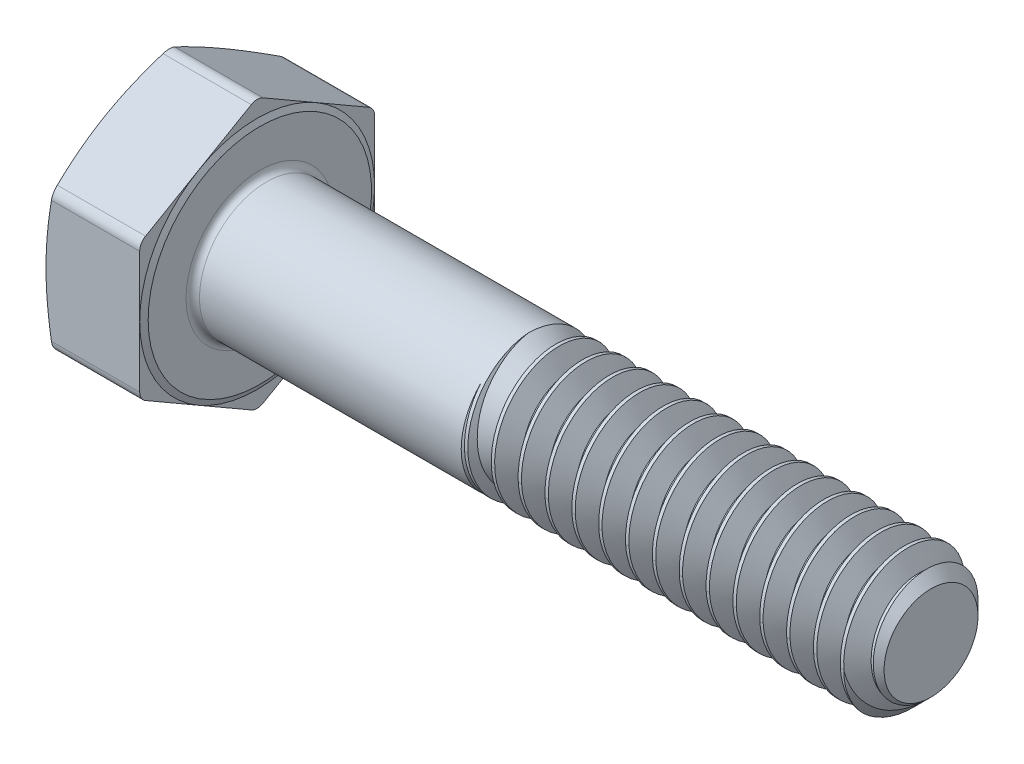
SolidWorks part; units mm, degrees
ref_plane "Front Plane" through (0, 0, 0) normal (0, 0, 1) x (1, 0, 0)
ref_plane "Top Plane" through (0, 0, 0) normal (0, 1, 0) x (1, 0, 0)
ref_plane "Right Plane" through (0, 0, 0) normal (1, 0, 0) x (0, 0, -1)
sketch "Sketch1" plane through (0, 0, 0) normal (0, 0, 1) x (1, 0, 0)
  line L0 (0, 0) -> (31.75, 0) construction
  line L1 (0, 0) -> (-4.7625, 0) construction
  line L2 (0, 5.5562) -> (0, -5.5562) construction
  line L3 (-4.7625, 5.5562) -> (-4.7625, -5.5563) construction
  line L4 (31.75, 3.175) -> (31.75, -3.175) construction
  line L5 (12.7, 3.175) -> (12.7, -3.175) construction
  line L8 (30.48, 3.175) -> (31.75, 3.175) construction
  point P8 (30.48, 0)
  point P11 (27.305, -3.175)
  point P12 (12.7, 0)
  point P15 (4.445, 0)
  point P16 (8.255, 0)
  dimension "Head Height" = 4.7625
  dimension "Head Width" = 11.1125
  dimension "Length" = 31.75
  dimension "Thread Size" = 6.35
  dimension "D1" = 4.445
  dimension "Thread Pitch" = 1.27
  dimension "Min. Thread Length" = 19.05
  dimension "D2" = 4.445
  dimension "D3" = 4.445
sketch "Sketch2" plane through (0, 0, 0) normal (1, 0, 0) x (0, 0, -1)
  circle A0 centre (0, 0) radius 3.175
extrude "Boss-Extrude1" add sketch "Sketch2" along normal up to vertex (31.75 mm away) up to point (31.75, 3.175, 0)
sketch "Sketch3" plane through (0, 0, 0) normal (-1, 0, 0) x (0, 0, 1)
  line L0 (0, 6.4158) -> (0, 0) construction
  line L1 (0, 6.4158) -> (-5.5562, 3.2079)
  line L2 (-5.5562, 3.2079) -> (-5.5562, -3.2079)
  line L3 (-5.5562, -3.2079) -> (0, -6.4158)
  line L4 (0, -6.4158) -> (5.5562, -3.2079)
  line L5 (5.5562, -3.2079) -> (5.5563, 3.2079)
  line L6 (5.5563, 3.2079) -> (0, 6.4158)
  circle A0 centre (0, 0) radius 5.5562 construction
extrude "Boss-Extrude2" add sketch "Sketch3" along normal up to vertex (4.7625 mm away) up to point (-4.7625, 5.5562, 0)
sketch "Sketch5" plane through (-4.7625, 0, 0) normal (-1, 0, 0) x (0, 0, 1)
  circle A0 centre (0, 0) radius 5.5562 construction
  circle A1 centre (0, 0) radius 5.5562 construction
  circle A2 centre (0, 0) radius 5.0006
  dimension "D1" = 0.5556
extrude "Cut-Extrude1" cut sketch "Sketch5" against normal up to vertex (4.7625 mm away) draft 70 flip side to cut up to point (0, 0, 0)
sketch "Sketch11" plane through (-4.7625, 0, 0) normal (-1, 0, 0) x (0, 0, 1)
  line L0 (0, 4.6672) -> (0, 2.9726) construction
  line L1 (0.1945, 4.6672) -> (0.1945, 2.9726)
  line L2 (-0.1945, 4.6672) -> (-0.1945, 2.9726)
  arc A0 (0.1945, 4.6672) -> (-0.1945, 4.6672) centre (0, 4.6672) ccw
  arc A1 (-0.1945, 2.9726) -> (0.1945, 2.9726) centre (0, 2.9726) ccw
  circle A2 centre (0, 0) radius 4.8617 construction
  circle A3 centre (0, 0) radius 2.7781 construction
  point P3 (0, 3.8199)
  dimension "D1" = 9.7234
  dimension "D2" = 5.5562
  dimension "D3" = 0.3889
extrude "Boss-Extrude5" add sketch "Sketch11" along normal blind 0.0635
fillet "Fillet5" radius 0.0635 4 edges at (-4.826, 3.8199, 0.1945) (-4.826, 2.7781, 0) (-4.826, 3.8199, -0.1945) (-4.826, 4.8617, 0)
fillet "Fillet6" radius 0.0635 4 edges at (-4.7625, 2.7781, 0) (-4.7625, 3.8199, -0.1945) (-4.7625, 4.8617, 0) (-4.7625, 3.8199, 0.1945)
pattern_circular "CirPattern1" count 9 over 360 about axis through (0, 0, 0) along (-1, 0, 0) of "Boss-Extrude5", "Fillet5", "Fillet6" reverse direction yes
sketch "Sketch16" plane through (-4.7625, 0, 0) normal (-1, 0, 0) x (0, 0, 1)
  circle A0 centre (0, 0) radius 2.5003
  dimension "D1" = 5.0006
extrude "Cut-Extrude2" cut sketch "Sketch16" against normal blind 0.508 draft 45
fillet "Fillet7" radius 0.5556 6 edges at (-2.1237, -6.4158, 0) (-2.1237, -3.2079, -5.5562) (-2.1237, 3.2079, -5.5562) (-2.1237, 6.4158, 0) (-2.1237, -3.2079, 5.5562) (-2.1237, 3.2079, 5.5563)
chamfer "Chamfer1" distance 0.9525 angle 45 1 edges at (31.75, 0, -3.175)
sketch "Sketch15" plane through (0, 0, 0) normal (0, 0, 1) x (1, 0, 0)
  line L0 (0, 5.2839) -> (-0.127, 5.5562)
  line L1 (0, 5.5562) -> (0, -5.5562) construction
  line L2 (-0.127, 5.5562) -> (-0.127, 6.4158)
  line L3 (-0.127, 6.4158) -> (0, 6.4158)
  line L4 (0, 6.4158) -> (0, 5.2839)
  line L5 (0, 3.2079) -> (0, 6.4158) construction
  dimension "D1" = 25
  dimension "D2" = 0.127
revolve "Cut-Revolve1" cut sketch "Sketch15" angle 360 about L0
fillet "Fillet4" radius 0.3175 1 edges at (0, 0, 3.175)
sketch "Reference Sketch1" plane through (0, 0, 0) normal (1, 0, 0) x (0, 0, -1)
  line L1 (0, 6.4158) -> (-5.5562, 3.2079)
  line L2 (-5.5562, 3.2079) -> (-5.5562, -3.2079)
  line L3 (-5.5562, -3.2079) -> (0, -6.4158)
  line L4 (0, -6.4158) -> (5.5562, -3.2079)
  line L5 (5.5562, -3.2079) -> (5.5562, 3.2079)
  line L6 (5.5562, 3.2079) -> (0, 6.4158)
  circle A0 centre (0, 0) radius 5.5563 construction
  circle A1 centre (0, 0) radius 5.5562
sketch "Sketch12" plane through (31.75, 0, 0) normal (1, 0, 0) x (0, 0, -1)
  circle A1 centre (0, 0) radius 3.175
ref_plane "Plane2" through (12.7, 0, 0) normal (1, 0, 0) x (0, 0, -1)
split "Split1" trim tools "Plane2" bodies to split 126 116 resulting bodies 118 119
curve "Helix/Spiral2" pitch 1.27 height 20.32 radius 3.175 centre (31.75, 0, 0) axis (-1, 0, 0) start towards (0, 1, 0) parameters "Pitch"=1.27
sketch "Sketch13" plane through (0, 0, 0) normal (0, 0, 1) x (1, 0, 0)
  line L0 (31.6706, 3.3125) -> (32.3056, 2.2126) construction
  line L1 (32.3056, 2.2126) -> (32.9406, 3.3125) construction
  line L2 (32.9406, 3.3125) -> (31.6706, 3.3125) construction
  line L3 (32.3056, 2.2126) -> (32.3056, 2.3501) construction
  line L4 (31.75, 3.175) -> (32.8612, 3.175)
  line L5 (32.3056, 3.175) -> (32.3056, 3.3125) construction
  line L6 (32.8612, 3.175) -> (32.385, 2.3501)
  line L7 (32.385, 2.3501) -> (32.2262, 2.3501)
  line L8 (32.2262, 2.3501) -> (31.75, 3.175)
  line L9 (30.48, 3.175) -> (31.75, 3.175) construction
  dimension "D1" = 0.1588
sweep "Cut-Sweep1" cut profiles "Sketch13" path "Helix/Spiral2" align with end faces yes
sketch "Sketch14" plane through (12.7, 0, 0) normal (1, 0, 0) x (0, 0, -1)
  circle A1 centre (0, 0) radius 3.175
  circle A2 centre (0, 0) radius 3.175
  dimension "D1" = 0
extrude "Boss-Extrude4" add sketch "Sketch14" along normal through all draft 31.8
equation "\"D1@Sketch11\"=\"Head Width@Sketch1\" * 0.875"
equation "\"D2@Sketch11\"=\"Head Width@Sketch1\"*0.5"
equation "\"D3@Sketch11\"=\"Head Width@Sketch1\" * .035"
equation "\"D3@Helix/Spiral2\"=\"Min. Thread Length@Sketch1\" + \"Thread Pitch@Sketch1\""
equation "\"Pitch@Helix/Spiral2\"=\"Thread Pitch@Sketch1\""
equation "\"D1@Sketch13\"=\"Thread Pitch@Sketch1\"*0.125"
equation "\"D1@Sketch5\"=\"Head Width@Sketch1\"*0.05"
equation "\"D1@Fillet4\"=\"Thread Size@Sketch1\"*0.05"
equation "\"D1@Sketch1\"=\"Thread Pitch@Sketch1\"*3.5"
equation "\"D1@Chamfer1\"=\"Thread Pitch@Sketch1\"*0.750"
equation "\"D1@Fillet7\"=\"Head Width@Sketch1\"*0.05"
equation "\"D2@Sketch1\"=\"D1@Sketch1\""
equation "\"D3@Sketch1\"=\"D1@Sketch1\""
equation "\"D1@Sketch16\"=\"Head Width@Sketch1\"*0.45"
